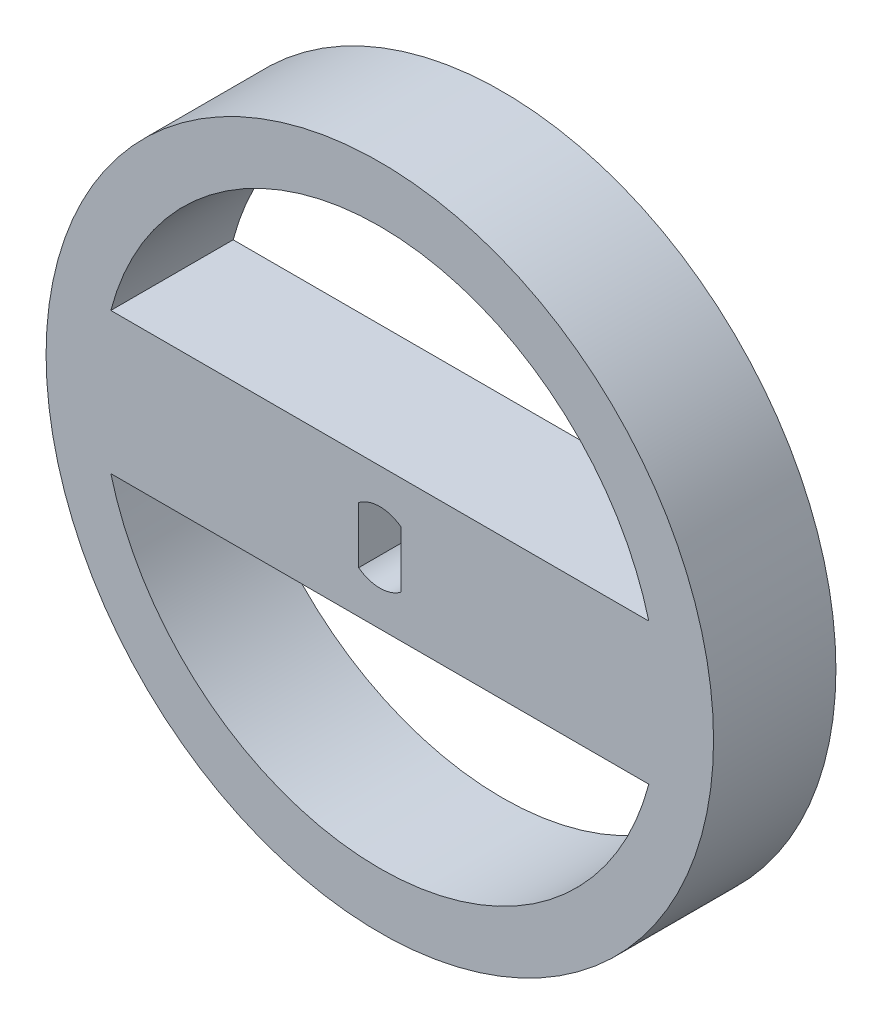
SolidWorks part; units mm, degrees
material "PET"
ref_plane "Front Plane" through (0, 0, 0) normal (0, 0, 1) x (1, 0, 0)
ref_plane "Top Plane" through (0, 0, 0) normal (0, 1, 0) x (1, 0, 0)
ref_plane "Right Plane" through (0, 0, 0) normal (1, 0, 0) x (0, 0, -1)
sketch "Sketch2" plane through (0, 0, 0) normal (0, 0, 1) x (1, 0, 0)
  line L1 (-149.0125, 105.9748) -> (-100.6523, 105.9748)
  line L2 (-149.0125, 105.9748) -> (-149.0125, 93.2748)
  line L3 (-149.0125, 93.2748) -> (-100.6523, 93.2748)
  line L4 (-100.6523, 105.9748) -> (-100.6523, 93.2748)
  line L5 (-149.0125, 105.9748) -> (-100.6523, 93.2748) construction
  line L6 (-149.0125, 93.2748) -> (-100.6523, 105.9748) construction
  line L7 (-126.7374, 102.1648) -> (-122.9274, 102.1648)
  line L8 (-126.7374, 102.1648) -> (-126.7374, 97.0848)
  line L9 (-126.7374, 97.0848) -> (-122.9274, 97.0848)
  line L10 (-122.9274, 102.1648) -> (-122.9274, 97.0848)
  line L11 (-126.7374, 102.1648) -> (-122.9274, 97.0848) construction
  line L12 (-126.7374, 97.0848) -> (-122.9274, 102.1648) construction
  circle A0 centre (-124.8324, 99.6248) radius 30
  circle A1 centre (-124.8324, 99.6248) radius 25
  circle A2 centre (-124.8324, 99.6248) radius 3.175
  dimension "D1" = 60
  dimension "D2" = 50
  dimension "D4" = 6.35
  dimension "D3" = 12.7
  dimension "D5" = 3.81
extrude "Boss-Extrude1" add sketch "Sketch2" against normal blind 11 contours A0 A1 | L4 L1 L2 L3 A2 | L2 A1 | L4 A1 | L8 A2 | L10 A2 | L7 A2 | L10 L7 L8 L9 | L9 A2 region at (-124.8324, 105.4748, 0) region at (-149.3409, 99.6248, 0) region at (-100.3239, 99.6248, 0) region at (-124.8324, 102.4211, 0) region at (-124.8324, 99.6248, 0) region at (-127.2553, 99.6248, 0) region at (-122.4096, 99.6248, 0) region at (-124.8324, 96.8285, 0) region at (-153.9839, 99.6248, 0)
extrude "Cut-Extrude1" cut sketch "Sketch2<3>" against normal blind 10 contours L10 L7 L8 L9 | L9 A2 | L7 A2 region at (-124.8324, 102.4211, 0) region at (-124.8324, 99.6248, 0) region at (-124.8324, 96.8285, 0)
sketch "Sketch2<3>" plane through (0, 0, 0) normal (0, 0, 1) x (1, 0, 0) same geometry as "Sketch2"
